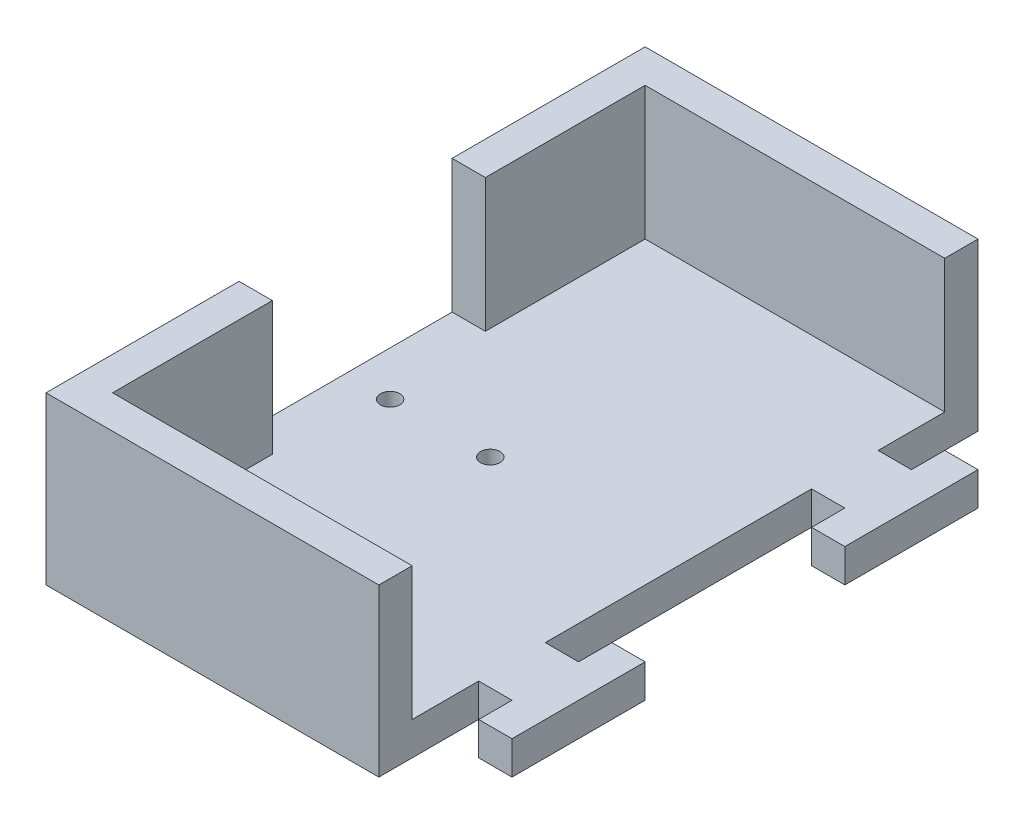
SolidWorks part; units mm, degrees
ref_plane "Front Plane" through (0, 0, 0) normal (0, 0, 1) x (1, 0, 0)
ref_plane "Top Plane" through (0, 0, 0) normal (0, 1, 0) x (1, 0, 0)
ref_plane "Right Plane" through (0, 0, 0) normal (1, 0, 0) x (0, 0, -1)
sketch "Sketch1" plane through (0, 0, 0) normal (0, 1, 0) x (1, 0, 0)
  line L1 (-38.1, -57.15) -> (25.4, -57.15)
  line L2 (-38.1, -57.15) -> (-38.1, 57.15)
  line L3 (-38.1, 57.15) -> (25.4, 57.15)
  line L4 (25.4, -57.15) -> (25.4, 57.15)
  line L5 (-38.1, -57.15) -> (25.4, 57.15) construction
  line L6 (-38.1, 57.15) -> (25.4, -57.15) construction
  point P0 (-6.35, 0)
  dimension "D1" = 63.5
  dimension "D2" = 114.3
  dimension "D3" = 6.35
extrude "Boss-Extrude1" add sketch "Sketch1" along normal blind 6.35
sketch "Sketch3" plane through (0, 6.35, 0) normal (0, 1, 0) x (1, 0, 0)
  line L0 (25.4, -57.15) -> (25.4, 57.15) construction
  line L1 (-38.1, 57.15) -> (25.4, 57.15)
  line L2 (-38.1, 57.15) -> (-38.1, 50.8)
  line L3 (-38.1, 50.8) -> (25.4, 50.8)
  line L4 (25.4, 57.15) -> (25.4, 50.8)
  line L6 (-38.1, -57.15) -> (25.4, -57.15)
  line L7 (-38.1, -57.15) -> (-38.1, -50.8)
  line L8 (-38.1, -50.8) -> (25.4, -50.8)
  line L9 (25.4, -57.15) -> (25.4, -50.8)
  dimension "D1" = 6.35
extrude "Boss-Extrude2" add sketch "Sketch3" along normal blind 25.4
sketch "Sketch6" plane through (0, 6.35, 0) normal (0, 1, 0) x (1, 0, 0)
  line L0 (25.4, -50.8) -> (25.4, 50.8) construction
  line L1 (25.4, 38.1) -> (31.75, 38.1)
  line L2 (25.4, 38.1) -> (25.4, 25.4)
  line L3 (25.4, 25.4) -> (31.75, 25.4)
  line L5 (25.4, 57.15) -> (-38.1, 57.15) construction
  line L6 (31.75, 44.45) -> (38.1, 44.45)
  line L7 (31.75, 44.45) -> (31.75, 38.1)
  line L8 (31.75, 19.05) -> (38.1, 19.05)
  line L9 (38.1, 44.45) -> (38.1, 19.05)
  line L10 (31.75, 25.4) -> (31.75, 19.05)
  point P10 (38.1, 31.75)
  point P11 (25.4, 31.75)
  dimension "D1" = 6.35
  dimension "D2" = 12.7
  dimension "D3" = 25.4
  dimension "D4" = 6.35
  dimension "D5" = 25.4
extrude "Boss-Extrude3" add sketch "Sketch6" against normal up to surface (6.35 mm away) up to face at (-6.35, 0, 0)
mirror "Mirror1" about plane through (0, 0, 0) normal (0, 0, 1) of "Boss-Extrude3"
sketch "Sketch7" plane through (0, 0, 0) normal (0, -1, 0) x (1, 0, 0)
  circle A0 centre (-10.5, 0) radius 1.85 construction
  circle A1 centre (-29.6, 0) radius 1.85 construction
  circle A2 centre (-10.5, 0) radius 1.85
  circle A3 centre (-29.6, 0) radius 1.85
extrude "Cut-Extrude1" cut sketch "Sketch7" against normal through all
sketch "Sketch8" plane through (0, 6.35, 0) normal (0, 1, 0) x (1, 0, 0)
  line L0 (-38.1, 57.15) -> (-38.1, 50.8) construction
  line L1 (-38.1, 50.8) -> (-31.75, 50.8)
  line L2 (-38.1, 50.8) -> (-38.1, 20.32)
  line L3 (-38.1, 20.32) -> (-31.75, 20.32)
  line L4 (-31.75, 50.8) -> (-31.75, 20.32)
  line L5 (-38.1, -50.8) -> (-31.75, -50.8)
  line L6 (-38.1, -50.8) -> (-38.1, -20.32)
  line L7 (-38.1, -20.32) -> (-31.75, -20.32)
  line L8 (-31.75, -50.8) -> (-31.75, -20.32)
  dimension "D1" = 40.64
extrude "Boss-Extrude4" add sketch "Sketch8" along normal up to surface (25.4 mm away) up to face at (-6.35, 31.75, 53.975)
